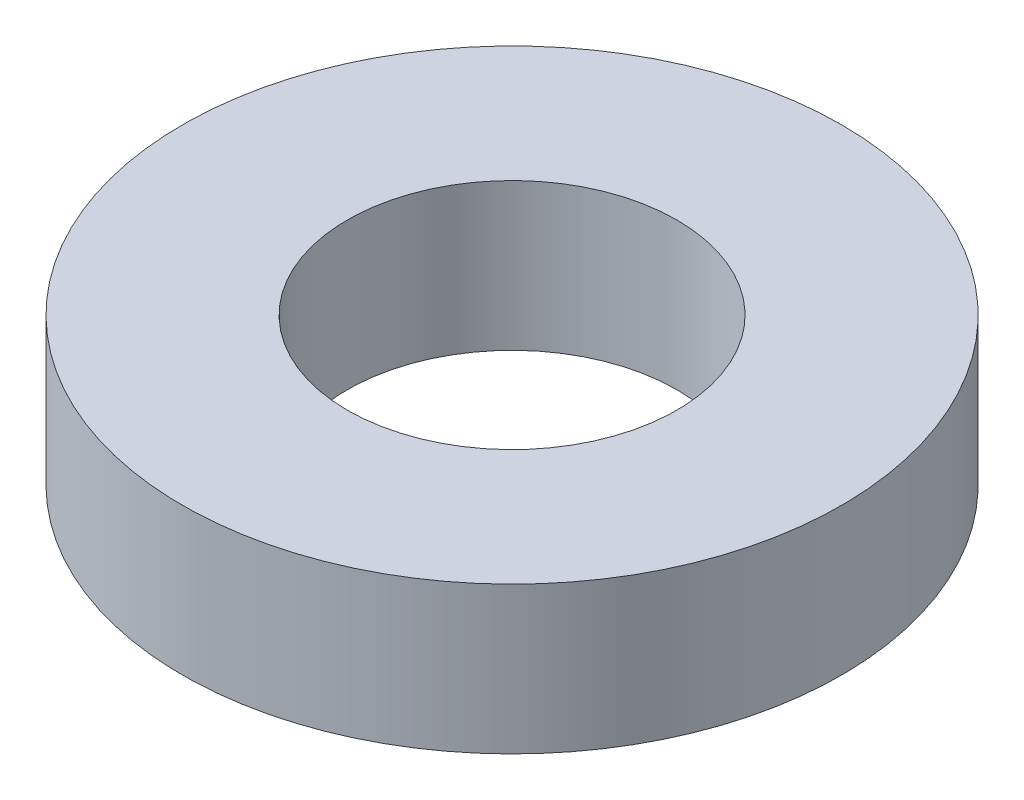
SolidWorks part; units mm, degrees
ref_plane "Front Plane" through (0, 0, 0) normal (0, 0, 1) x (1, 0, 0)
ref_plane "Top Plane" through (0, 0, 0) normal (0, 1, 0) x (1, 0, 0)
ref_plane "Right Plane" through (0, 0, 0) normal (1, 0, 0) x (0, 0, -1)
sketch "Sketch1" plane through (0, 0, 0) normal (0, 1, 0) x (1, 0, 0)
  circle A0 centre (0, 0) radius 65
  dimension "FLANGE_OD" = 130
extrude "Boss-Extrude1" add sketch "Sketch1" along normal blind 29
sketch "Sketch2" plane through (0, 0, 0) normal (0, 1, 0) x (1, 0, 0)
  circle A0 centre (0, 0) radius 32.5
  dimension "BORE_D" = 65
extrude "Cut-Extrude1" cut sketch "Sketch2" along normal through all
sketch "Sketch3" plane through (0, 29, 0) normal (0, 1, 0) x (1, 0, 0)
  circle A0 centre (0, 0) radius 28.7561 construction
  circle A1 centre (-28.7561, 0) radius 1.8364
  dimension "BOLT_D" = 3.6727
  dimension "BOLT_PCD" = 57.5123
extrude "Cut-Extrude2" cut sketch "Sketch3" against normal blind 26.704 rebuild error yes
pattern_circular "CirPattern1" count 3 over 360 rebuild error yes
